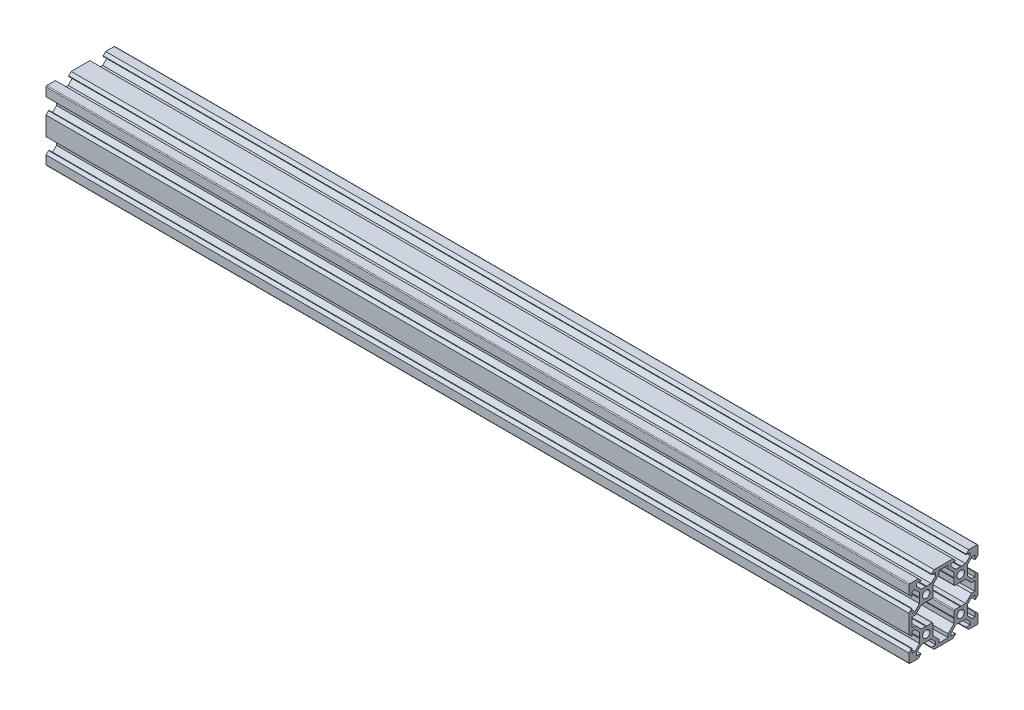
SolidWorks part; units mm, degrees
material "6061-T6 (SS)"
ref_plane "Top" through (0, 0, 0) normal (0, 0, 1) x (1, 0, 0)
ref_plane "Front" through (0, 0, 0) normal (0, 1, 0) x (1, 0, 0)
ref_plane "Right" through (0, 0, 0) normal (1, 0, 0) x (0, 0, -1)
sketch "Profile Sketch" plane through (0, 0, 0) normal (1, 0, 0) x (0, 0, -1)
  line L0 (0, 10) -> (-5.42, 10)
  line L1 (-4.5, 8.2) -> (-4.5, 6.56)
  line L2 (-4.5, 6.56) -> (-7.16, 3.9)
  line L3 (-7.16, 3.9) -> (-9.79, 3.9)
  line L4 (-9.79, 3.9) -> (-10, 3.69)
  line L5 (2.7, 8.2) -> (-2.7, 8.2)
  line L6 (-2.7, 8.2) -> (-2.7, 6.2387)
  line L7 (-2.7, 6.2387) -> (-6.1, 2.8387)
  line L8 (-6.1, 2.8387) -> (-6.1, 0.21)
  line L9 (-6.875, 8.545) -> (-6.875, 8.2)
  line L10 (-6.875, 8.2) -> (-4.5, 8.2)
  line L11 (-6.875, 8.545) -> (-5.42, 10)
  line L12 (0, -10) -> (0, 10) construction
  line L13 (-20, 0) -> (20, 0) construction
  line L14 (-10, -10) -> (-10, 10) construction
  line L21 (-6.6, -3.9) -> (-9.79, -3.9)
  line L25 (-10, 0) -> (-20, 10) construction
  line L26 (-18.545, 3.125) -> (-18.2, 3.125)
  line L31 (-16.2383, -7.3) -> (-12.84, -3.9)
  line L32 (-12.84, -3.9) -> (-10.21, -3.9)
  line L33 (-20, 4.58) -> (-20, 9.5)
  line L34 (-13.9, 2.8387) -> (-13.9, 0.21)
  line L35 (-16.56, 5.5) -> (-13.9, 2.8387)
  line L36 (-12.84, 3.9) -> (-10.21, 3.9)
  line L37 (-15.5, 6.56) -> (-12.84, 3.9)
  line L38 (-15.5, 8.2) -> (-15.5, 6.56)
  line L39 (-13.125, 8.545) -> (-14.58, 10)
  line L40 (-13.125, 8.2) -> (-15.5, 8.2)
  line L41 (-13.125, 8.545) -> (-13.125, 8.2)
  line L42 (-18.2, 3.125) -> (-18.2, 5.5)
  line L43 (-18.545, 3.125) -> (-20, 4.58)
  line L44 (-18.2, 5.5) -> (-16.56, 5.5)
  line L45 (-14.58, 10) -> (-19.5, 10)
  line L46 (-16.56, -5.5) -> (-13.9, -2.8387)
  line L48 (-18.2, -5.5) -> (-16.56, -5.5)
  line L49 (-18.545, -3.125) -> (-20, -4.58)
  line L50 (-18.2, -3.125) -> (-18.2, -5.5)
  line L51 (-20, -4.58) -> (-20, -15.42)
  line L52 (-18.545, -3.125) -> (-18.2, -3.125)
  line L53 (9.79, -3.9) -> (10, -3.69)
  line L99 (-10, 3.69) -> (-10.21, 3.9)
  line L100 (-10, -3.69) -> (-10.21, -3.9)
  line L101 (-9.79, -3.9) -> (-10, -3.69)
  line L102 (-13.9, -0.21) -> (-13.69, 0)
  line L103 (-13.69, 0) -> (-13.9, 0.21)
  line L104 (-13.9, -0.21) -> (-13.9, -2.8387)
  line L105 (-6.1, -0.21) -> (-6.31, 0)
  line L106 (-6.31, 0) -> (-6.1, -0.21)
  line L107 (-6.1, -0.21) -> (-6.1, -3.4)
  line L117 (-16.2383, -7.3) -> (-18.2, -7.3)
  line L118 (20, -10) -> (20, 10) construction
  line L119 (20, -10) -> (-20, -10) construction
  line L120 (-20, -10) -> (-20, 10) construction
  line L121 (20, 10) -> (-20, 10) construction
  line L122 (6.6, -3.9) -> (9.79, -3.9)
  line L123 (10, -3.69) -> (10.21, -3.9)
  line L124 (-18.2, -7.3) -> (-18.2, -12.7)
  line L125 (12.84, -3.9) -> (10.21, -3.9)
  line L126 (-6.31, 0) -> (-6.1, 0.21)
  line L127 (16.2383, -7.3) -> (12.84, -3.9)
  line L128 (20, -4.58) -> (20, -15.42)
  line L129 (18.2, -7.3) -> (18.2, -12.7)
  line L130 (16.2383, -7.3) -> (18.2, -7.3)
  line L131 (18.545, -3.125) -> (18.2, -3.125)
  line L132 (18.2, -3.125) -> (18.2, -5.5)
  line L133 (18.545, -3.125) -> (20, -4.58)
  line L134 (18.2, -5.5) -> (16.56, -5.5)
  line L135 (16.56, -5.5) -> (13.9, -2.8387)
  line L136 (13.9, -0.21) -> (13.9, -2.8387)
  line L137 (13.69, 0) -> (13.9, 0.21)
  line L138 (13.9, -0.21) -> (13.69, 0)
  line L139 (13.9, 2.8387) -> (13.9, 0.21)
  line L140 (18.2, 5.5) -> (16.56, 5.5)
  line L141 (18.545, 3.125) -> (20, 4.58)
  line L142 (18.2, 3.125) -> (18.2, 5.5)
  line L143 (16.56, 5.5) -> (13.9, 2.8387)
  line L144 (18.545, 3.125) -> (18.2, 3.125)
  line L145 (20, 4.58) -> (20, 9.5)
  line L146 (14.58, 10) -> (19.5, 10)
  line L147 (13.125, 8.545) -> (13.125, 8.2)
  line L148 (13.125, 8.2) -> (15.5, 8.2)
  line L149 (13.125, 8.545) -> (14.58, 10)
  line L150 (15.5, 8.2) -> (15.5, 6.56)
  line L151 (15.5, 6.56) -> (12.84, 3.9)
  line L152 (12.84, 3.9) -> (10.21, 3.9)
  line L153 (10, 3.69) -> (10.21, 3.9)
  line L154 (9.79, 3.9) -> (10, 3.69)
  line L155 (6.1, -0.21) -> (6.1, -3.4)
  line L156 (6.1, -0.21) -> (6.31, 0)
  line L157 (6.31, 0) -> (6.1, 0.21)
  line L158 (6.1, 2.8387) -> (6.1, 0.21)
  line L159 (7.16, 3.9) -> (9.79, 3.9)
  line L160 (2.7, 6.2387) -> (6.1, 2.8387)
  line L161 (4.5, 6.56) -> (7.16, 3.9)
  line L162 (6.875, 8.545) -> (6.875, 8.2)
  line L163 (6.875, 8.2) -> (4.5, 8.2)
  line L164 (4.5, 8.2) -> (4.5, 6.56)
  line L165 (2.7, 8.2) -> (2.7, 6.2387)
  line L166 (6.875, 8.545) -> (5.42, 10)
  line L167 (0, 10) -> (5.42, 10)
  line L168 (-20, -24.58) -> (-20, -29.5)
  line L169 (-14.58, -30) -> (-19.5, -30)
  line L170 (-7.16, -23.9) -> (-9.79, -23.9)
  line L171 (-10, -23.69) -> (-10.21, -23.9)
  line L172 (-9.79, -23.9) -> (-10, -23.69)
  line L173 (-12.84, -23.9) -> (-10.21, -23.9)
  line L174 (-13.125, -28.545) -> (-13.125, -28.2)
  line L175 (-13.125, -28.2) -> (-15.5, -28.2)
  line L176 (-13.125, -28.545) -> (-14.58, -30)
  line L177 (-15.5, -28.2) -> (-15.5, -26.56)
  line L178 (-15.5, -26.56) -> (-12.84, -23.9)
  line L179 (-18.2, -25.5) -> (-16.56, -25.5)
  line L180 (-18.545, -23.125) -> (-20, -24.58)
  line L181 (-18.2, -23.125) -> (-18.2, -25.5)
  line L182 (-16.56, -25.5) -> (-13.9, -22.8387)
  line L183 (-18.545, -23.125) -> (-18.2, -23.125)
  line L184 (-13.9, -19.79) -> (-13.9, -17.1613)
  line L185 (-13.69, -20) -> (-13.9, -20.21)
  line L186 (-13.9, -19.79) -> (-13.69, -20)
  line L187 (-13.9, -22.8387) -> (-13.9, -20.21)
  line L188 (-16.2383, -12.7) -> (-18.2, -12.7)
  line L189 (-18.545, -16.875) -> (-18.2, -16.875)
  line L190 (-18.2, -16.875) -> (-18.2, -14.5)
  line L191 (-18.545, -16.875) -> (-20, -15.42)
  line L192 (-18.2, -14.5) -> (-16.56, -14.5)
  line L193 (-16.56, -14.5) -> (-13.9, -17.1613)
  line L194 (-16.2383, -12.7) -> (-12.84, -16.1)
  line L195 (-9.79, -16.1) -> (-10, -16.31)
  line L196 (-10, -16.31) -> (-10.21, -16.1)
  line L197 (-12.84, -16.1) -> (-10.21, -16.1)
  line L198 (-6.6, -16.1) -> (-9.79, -16.1)
  line L199 (-6.1, -19.79) -> (-6.1, -16.6)
  line L200 (-6.1, -22.8387) -> (-6.1, -20.21)
  line L201 (-6.31, -20) -> (-6.1, -20.21)
  line L202 (-6.31, -20) -> (-6.1, -19.79)
  line L203 (-6.1, -19.79) -> (-6.31, -20)
  line L204 (-2.7, -26.2387) -> (-6.1, -22.8387)
  line L205 (-4.5, -26.56) -> (-7.16, -23.9)
  line L206 (-4.5, -28.2) -> (-4.5, -26.56)
  line L207 (-6.875, -28.2) -> (-4.5, -28.2)
  line L208 (-6.875, -28.545) -> (-6.875, -28.2)
  line L209 (-6.875, -28.545) -> (-5.42, -30)
  line L210 (0, -30) -> (-5.42, -30)
  line L211 (0, -30) -> (5.42, -30)
  line L212 (14.58, -30) -> (19.5, -30)
  line L213 (20, -24.58) -> (20, -29.5)
  line L214 (6.875, -28.545) -> (5.42, -30)
  line L215 (2.7, -28.2) -> (2.7, -26.2387)
  line L216 (4.5, -28.2) -> (4.5, -26.56)
  line L217 (6.875, -28.2) -> (4.5, -28.2)
  line L218 (6.875, -28.545) -> (6.875, -28.2)
  line L219 (4.5, -26.56) -> (7.16, -23.9)
  line L220 (2.7, -26.2387) -> (6.1, -22.8387)
  line L221 (7.16, -23.9) -> (9.79, -23.9)
  line L222 (6.1, -22.8387) -> (6.1, -20.21)
  line L223 (9.79, -23.9) -> (10, -23.69)
  line L224 (10, -23.69) -> (10.21, -23.9)
  line L225 (12.84, -23.9) -> (10.21, -23.9)
  line L226 (15.5, -26.56) -> (12.84, -23.9)
  line L227 (15.5, -28.2) -> (15.5, -26.56)
  line L228 (13.125, -28.545) -> (14.58, -30)
  line L229 (13.125, -28.2) -> (15.5, -28.2)
  line L230 (13.125, -28.545) -> (13.125, -28.2)
  line L231 (18.545, -23.125) -> (18.2, -23.125)
  line L232 (16.56, -25.5) -> (13.9, -22.8387)
  line L233 (18.2, -23.125) -> (18.2, -25.5)
  line L234 (18.545, -23.125) -> (20, -24.58)
  line L235 (18.2, -25.5) -> (16.56, -25.5)
  line L236 (13.9, -22.8387) -> (13.9, -20.21)
  line L237 (2.7, -28.2) -> (-2.7, -28.2)
  line L238 (6.31, -20) -> (6.1, -20.21)
  line L239 (6.1, -19.79) -> (6.31, -20)
  line L240 (13.9, -19.79) -> (13.69, -20)
  line L241 (13.69, -20) -> (13.9, -20.21)
  line L242 (6.1, -19.79) -> (6.1, -16.6)
  line L243 (13.9, -19.79) -> (13.9, -17.1613)
  line L244 (16.56, -14.5) -> (13.9, -17.1613)
  line L245 (18.2, -14.5) -> (16.56, -14.5)
  line L246 (18.545, -16.875) -> (20, -15.42)
  line L247 (18.2, -16.875) -> (18.2, -14.5)
  line L248 (18.545, -16.875) -> (18.2, -16.875)
  line L249 (16.2383, -12.7) -> (18.2, -12.7)
  line L250 (16.2383, -12.7) -> (12.84, -16.1)
  line L251 (12.84, -16.1) -> (10.21, -16.1)
  line L252 (10, -16.31) -> (10.21, -16.1)
  line L253 (6.6, -16.1) -> (9.79, -16.1)
  line L254 (9.79, -16.1) -> (10, -16.31)
  line L255 (-2.7, -26.2387) -> (-2.7, -28.2)
  circle A0 centre (-10, 0) radius 2.1
  arc A1 (-19.5, 10) -> (-20, 9.5) centre (-19.5, 9.5) ccw
  arc A2 (-6.6, -3.9) -> (-6.1, -3.4) centre (-6.6, -3.4) ccw
  arc A3 (6.6, -3.9) -> (6.1, -3.4) centre (6.6, -3.4) cw
  circle A4 centre (10, 0) radius 2.1
  arc A5 (19.5, 10) -> (20, 9.5) centre (19.5, 9.5) cw
  arc A6 (-19.5, -30) -> (-20, -29.5) centre (-19.5, -29.5) cw
  arc A7 (-6.6, -16.1) -> (-6.1, -16.6) centre (-6.6, -16.6) cw
  arc A8 (19.5, -30) -> (20, -29.5) centre (19.5, -29.5) ccw
  circle A9 centre (10, -20) radius 2.1
  arc A10 (6.6, -16.1) -> (6.1, -16.6) centre (6.6, -16.6) ccw
  circle A11 centre (-10, -20) radius 2.1
  point P35 (-2.4957, 0)
  point P119 (0, 18.9743)
  point P121 (0, 8.2)
  point P123 (2.4957, 0)
  point P131 (0, 0)
  point P143 (0, 0)
  point P164 (-18.2, -10)
  point P234 (18.2, -10)
  dimension "D4" = 5.42
  dimension "D5" = 40
  dimension "D6" = 4.2
  dimension "D16" = 0.5
  dimension "D17" = 0.5
  dimension "D2" = 45
  dimension "D3" = 20
  dimension "D7" = 1.5
  dimension "D9" = 10
  dimension "D10" = 3.9
  dimension "D11" = 3.9
  dimension "D13" = 3.125
  dimension "D14" = 5.5
  dimension "D15" = 1.64
  dimension "Knotch Depth" = 0.21
extrude "Profile Extrude" add sketch "Profile Sketch" along normal blind 500 contours L0 L11 L9 L10 L1 L2 L3 L4 L99 L36 L37 L38 L40 L41 L39 L45 A1 L33 L43 L26 L42 L44 L35 L34 L103 L102 L104 L46 L48 L50 L52 L49 L51 region at (0, 9.4343, -2.71)
equation "\"M2x0.4_Close_Hole\"= 2.2"
equation "\"M2.5x0.45_Close_Hole\"= 2.7"
equation "\"M3x0.5_Close_Hole\"= 3.2"
equation "\"M4x0.7_Close_Hole\"= 4.3"
equation "\"M5x0.8_Close_Hole\"= 5.3"
equation "\"M6x1_Close_Hole\"= 6.3"
equation "\"M7x1_Close_Hole\"= 7.4"
equation "\"M8x1.25_Close_Hole\"= 8.4"
equation "\"M2x0.4_Tap_Hole_75\"= 1.6"
equation "\"M3x0.5_Tap_Hole_75\"= 2.5"
equation "\"M4x0.7_Tap_Hole_75\"= 3.3"
equation "\"M5x0.8_Tap_Hole_75\"= 4.2"
equation "\"M6x1_Tap_Hole_75\"= 5"
equation "\"M7x1_Tap_Hole_75\"= 6"
equation "\"M8x1.25_Tap_Hole_75\"= 6.8"
